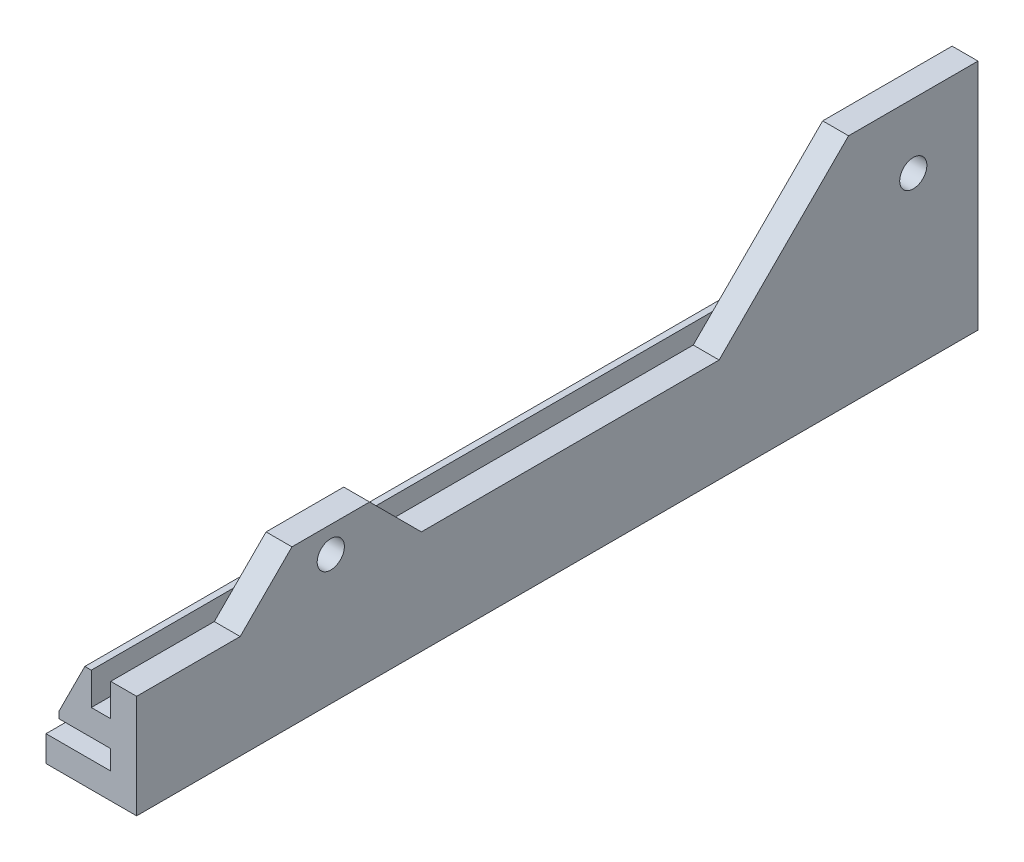
SolidWorks part; units mm, degrees
material "ABS"
ref_plane "Płaszczyzna przednia" through (0, 0, 0) normal (0, 0, 1) x (1, 0, 0)
ref_plane "Płaszczyzna górna" through (0, 0, 0) normal (0, 1, 0) x (1, 0, 0)
ref_plane "Płaszczyzna prawa" through (0, 0, 0) normal (1, 0, 0) x (0, 0, -1)
sketch "Szkic1" plane through (0, 0, 0) normal (0, 0, 1) x (1, 0, 0)
  line L0 (0, 0) -> (14, 0)
  line L1 (0, 0) -> (0, 16)
  line L2 (14, 0) -> (14, 4)
  line L3 (14, 4) -> (4, 4)
  line L4 (4, 4) -> (4, 7)
  line L5 (4, 7) -> (12, 7)
  line L6 (0, 16) -> (4, 16)
  line L7 (4, 16) -> (4, 11)
  line L8 (4, 11) -> (7, 11)
  line L9 (7, 11) -> (7, 16)
  line L11 (7, 16) -> (8, 16)
  line L12 (8, 16) -> (12, 8)
  line L13 (12, 8) -> (12, 7)
  point P12 (4, 5.5)
  dimension "D1" = 14
  dimension "D2" = 16
  dimension "D3" = 4
  dimension "D4" = 3
  dimension "D5" = 4
  dimension "D6" = 4
  dimension "D7" = 3
  dimension "D8" = 8
  dimension "D9" = 5
  dimension "D10" = 1
  dimension "D11" = 1
extrude "Dodanie-wyciągnięcie1" add sketch "Szkic1" along normal blind 130
sketch "Szkic2" plane through (0, 0, 0) normal (-1, 0, 0) x (0, 0, 1)
  line L0 (20, 36) -> (40, 16)
  line L1 (0, 16) -> (20, 16)
  line L2 (0, 16) -> (0, 36)
  line L3 (0, 36) -> (20, 36)
  line L5 (130, 16) -> (0, 16) construction
  line L6 (40, 16) -> (20, 16)
  line L7 (106, 16) -> (106, 24)
  line L8 (106, 24) -> (94, 24)
  line L9 (94, 24) -> (94, 16)
  line L10 (94, 16) -> (106, 16)
  line L11 (130, 16) -> (130, 0) construction
  circle A0 centre (10, 26) radius 2.1
  circle A1 centre (100, 20) radius 2.1
  dimension "D5" = 4.2
  dimension "D1" = 20
  dimension "D2" = 20
  dimension "D3" = 10
  dimension "D4" = 10
  dimension "D6" = 20
  dimension "D7" = 40
  dimension "D8" = 4
  dimension "D9" = 6
  dimension "D10" = 6
  dimension "D11" = 30
  dimension "D12" = 8
extrude "Dodanie-wyciągnięcie2" add sketch "Szkic2" against normal blind 4
chamfer "Sfazowanie1" distance 8 angle 45 2 edges at (2, 16, 94) (2, 16, 106)
mirror "Lustro1" about plane through (0, 0, 130) normal (1, 0, 0) of bodies 104
sketch "Szkic3" plane through (0, 0, 130) normal (0, 0, 1) x (1, 0, 0)
  line L1 (0, 0) -> (20.3135, 0)
  line L2 (0, 0) -> (0, 37.2085)
  line L3 (0, 37.2085) -> (20.3135, 37.2085)
  line L4 (20.3135, 0) -> (20.3135, 37.2085)
extrude "Wytnij-wyciągnięcie1" cut sketch "Szkic3" against normal through all
